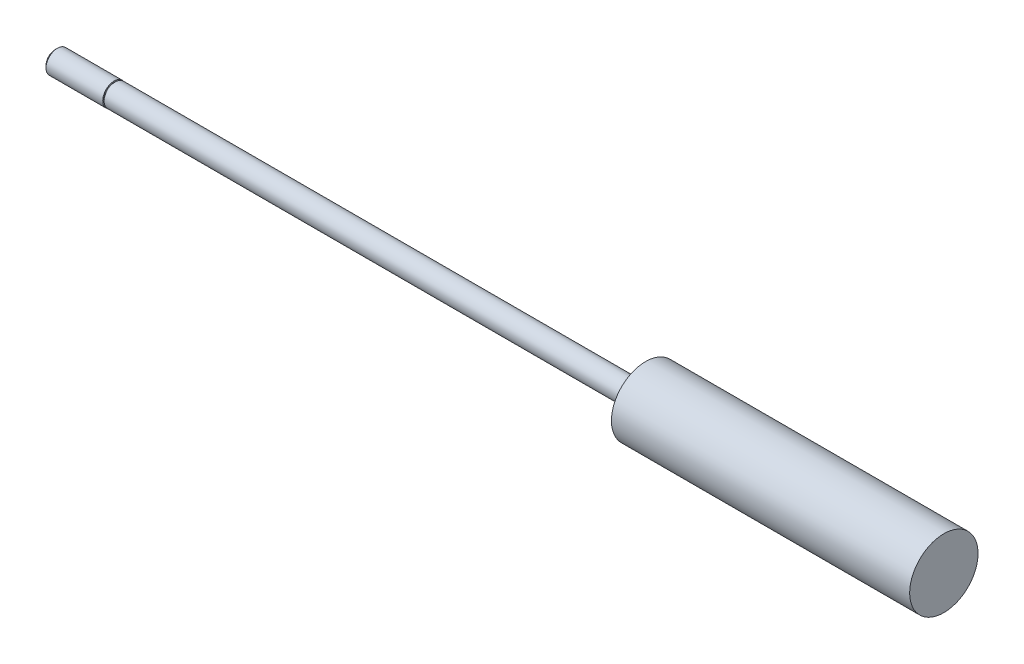
SolidWorks part; units mm, degrees
material "AISI 1045 Steel, cold drawn"
ref_plane "Front Plane" through (0, 0, 0) normal (0, 0, 1) x (1, 0, 0)
ref_plane "Top Plane" through (0, 0, 0) normal (0, 1, 0) x (1, 0, 0)
ref_plane "Right Plane" through (0, 0, 0) normal (1, 0, 0) x (0, 0, -1)
sketch "Sketch1" plane through (0, 0, 0) normal (0, 0, 1) x (1, 0, 0)
  line L0 (0, 0) -> (0, 2.3749)
  line L1 (0, 2.3749) -> (111.9124, 2.3749)
  line L2 (111.9124, 2.3749) -> (111.9124, 7.2199)
  line L3 (111.9124, 7.2199) -> (174.8536, 7.2199)
  line L4 (174.8536, 7.2199) -> (174.8536, 0)
  line L5 (174.8536, 0) -> (0, 0)
  line L6 (174.8536, 0) -> (0, 0) construction
revolve "Revolve1" add sketch "Sketch1" angle 360 about L6 reverse direction yes
sketch "Sketch2" plane through (0, 0, 0) normal (0, 0, 1) x (1, 0, 0)
  line L0 (-12.7, 0) -> (-12.7, 1.9406)
  line L1 (-12.7, 1.9406) -> (-12.2276, 2.413)
  line L2 (-12.2276, 2.413) -> (0, 2.413)
  line L3 (0, 2.413) -> (0, 0)
  line L4 (0, 0) -> (-12.7, 0)
  line L5 (0, 0) -> (-12.7, 0) construction
revolve "Revolve2" add sketch "Sketch2" angle 360 about L5 reverse direction yes
cosmetic thread "Cosmetic Thread1" parameters "D1"=12.7, "D2"=3.8811
ref_plane "Plane1" through (0, 0, 0) normal (1, 0, 0) x (0, 0, -1)
ref_plane "Plane2" through (0, 0, 0) normal (1, 0, 0) x (0, 0, -1)
ref_plane "Plane3" through (286.766, 0, 0) normal (1, 0, 0) x (0, 0, -1)
ref_plane "Plane4" through (-12.7, 0, 0) normal (1, 0, 0) x (0, 0, -1)
sketch "Sketch3" plane through (0, 0, 0) normal (0, 0, 1) x (1, 0, 0)
  line L0 (-0.254, 2.667) -> (-0.254, 2.159)
  line L1 (-0.254, 2.159) -> (0, 2.159)
  line L2 (0, 2.159) -> (0, 2.667)
  line L3 (0, 2.667) -> (-0.254, 2.667)
  line L4 (0, 0) -> (-0.254, 0) construction
revolve "Cut-Revolve1" cut sketch "Sketch3" angle 360 about L4 reverse direction yes
ref_plane "Plane5" through (0, 0, 0) normal (1, 0, 0) x (0, 0, -1)
ref_plane "Plane6" through (-12.7, 0, 0) normal (1, 0, 0) x (0, 0, -1)
ref_plane "dia1 XY" through (0, 0, 0) normal (1, 0, 0) x (0, 0, -1)
ref_plane "dia1 XZ" through (0, 2.3749, 0) normal (0, -1, 0) x (-1, 0, 0)
ref_plane "dia1 YZ" through (0, 0, 0) normal (0, 0, -1) x (-1, 0, 0)
ref_axis "dia1 X" through (0, 2.3749, 80.9) along (0, 0, -1)
ref_axis "dia1 Y" through (0, -50, 0) along (0, 1, 0)
ref_axis "dia1 Z" through (80.9, 2.3749, 0) along (-1, 0, 0)
sketch3d "dia1"
  point P0 (0, 2.3749, 0)
ref_plane "dia12 XY" through (0, 0, 0) normal (1, 0, 0) x (0, 0, -1)
ref_plane "dia12 XZ" through (0, 0, 0) normal (0, -1, 0) x (-1, 0, 0)
ref_plane "dia12 YZ" through (0, 0, 7.8105) normal (0, 0, -1) x (-1, 0, 0)
ref_axis "dia12 X" through (0, 0, 80.9) along (0, 0, -1)
ref_axis "dia12 Y" through (0, -50, 7.8105) along (0, 1, 0)
ref_axis "dia12 Z" through (80.9, 0, 7.8105) along (-1, 0, 0)
sketch3d "dia12"
  point P0 (0, 0, 7.8105)
ref_plane "dia2 XY" through (0, 0, 0) normal (1, 0, 0) x (0, 0, -1)
ref_plane "dia2 XZ" through (0, -2.3749, 0) normal (0, -1, 0) x (-1, 0, 0)
ref_plane "dia2 YZ" through (0, 0, 0) normal (0, 0, -1) x (-1, 0, 0)
ref_axis "dia2 X" through (0, -2.3749, 80.9) along (0, 0, -1)
ref_axis "dia2 Y" through (0, -50, 0) along (0, 1, 0)
ref_axis "dia2 Z" through (80.9, -2.3749, 0) along (-1, 0, 0)
sketch3d "dia2"
  point P0 (0, -2.3749, 0)
ref_plane "dia22 XY" through (0, 0, 0) normal (1, 0, 0) x (0, 0, -1)
ref_plane "dia22 XZ" through (0, 0, 0) normal (0, -1, 0) x (-1, 0, 0)
ref_plane "dia22 YZ" through (0, 0, -7.8105) normal (0, 0, -1) x (-1, 0, 0)
ref_axis "dia22 X" through (0, 0, 80.9) along (0, 0, -1)
ref_axis "dia22 Y" through (0, -50, -7.8105) along (0, 1, 0)
ref_axis "dia22 Z" through (80.9, 0, -7.8105) along (-1, 0, 0)
sketch3d "dia22"
  point P0 (0, 0, -7.8105)
ref_plane "rl1 XY" through (-12.7, 0, 0) normal (1, 0, 0) x (0, 0, -1)
ref_plane "rl1 XZ" through (0, 0, 0) normal (0, -1, 0) x (-1, 0, 0)
ref_plane "rl1 YZ" through (0, 0, 0) normal (0, 0, -1) x (-1, 0, 0)
ref_axis "rl1 X" through (-12.7, 0, 80.9) along (0, 0, -1)
ref_axis "rl1 Y" through (-12.7, -50, 0) along (0, 1, 0)
ref_axis "rl1 Z" through (80.9, 0, 0) along (-1, 0, 0)
sketch3d "rl1"
  point P0 (-12.7, 0, 0)
ref_plane "rl2 XY" through (0, 0, 0) normal (1, 0, 0) x (0, 0, -1)
ref_plane "rl2 XZ" through (0, 0, 0) normal (0, -1, 0) x (-1, 0, 0)
ref_plane "rl2 YZ" through (0, 0, 0) normal (0, 0, -1) x (-1, 0, 0)
ref_axis "rl2 X" through (0, 0, 80.9) along (0, 0, -1)
ref_axis "rl2 Y" through (0, -50, 0) along (0, 1, 0)
ref_axis "rl2 Z" through (80.9, 0, 0) along (-1, 0, 0)
sketch3d "rl2"
  point P0 (0, 0, 0)
ref_plane "rod_cp XY" through (0, 0, 0) normal (1, 0, 0) x (0, 0, -1)
ref_plane "rod_cp XZ" through (0, 0, 0) normal (0, -1, 0) x (-1, 0, 0)
ref_plane "rod_cp YZ" through (0, 0, 0) normal (0, 0, -1) x (-1, 0, 0)
ref_axis "rod_cp X" through (0, 0, 80.9) along (0, 0, -1)
ref_axis "rod_cp Y" through (0, -50, 0) along (0, 1, 0)
ref_axis "rod_cp Z" through (80.9, 0, 0) along (-1, 0, 0)
sketch3d "rod_cp"
  point P0 (0, 0, 0)
ref_plane "thd1 XY" through (-12.7, 0, 0) normal (1, 0, 0) x (0, 0, -1)
ref_plane "thd1 XZ" through (0, 2.413, 0) normal (0, -1, 0) x (-1, 0, 0)
ref_plane "thd1 YZ" through (0, 0, 0) normal (0, 0, -1) x (-1, 0, 0)
ref_axis "thd1 X" through (-12.7, 2.413, 80.9) along (0, 0, -1)
ref_axis "thd1 Y" through (-12.7, -50, 0) along (0, 1, 0)
ref_axis "thd1 Z" through (80.9, 2.413, 0) along (-1, 0, 0)
sketch3d "thd1"
  point P0 (-12.7, 2.413, 0)
ref_plane "thd2 XY" through (-12.7, 0, 0) normal (1, 0, 0) x (0, 0, -1)
ref_plane "thd2 XZ" through (0, -2.413, 0) normal (0, -1, 0) x (-1, 0, 0)
ref_plane "thd2 YZ" through (0, 0, 0) normal (0, 0, -1) x (-1, 0, 0)
ref_axis "thd2 X" through (-12.7, -2.413, 80.9) along (0, 0, -1)
ref_axis "thd2 Y" through (-12.7, -50, 0) along (0, 1, 0)
ref_axis "thd2 Z" through (80.9, -2.413, 0) along (-1, 0, 0)
sketch3d "thd2"
  point P0 (-12.7, -2.413, 0)
ref_plane "to_rod_clevis XY" through (-12.7, 0, 0) normal (1, 0, 0) x (0, 0, -1)
ref_plane "to_rod_clevis XZ" through (0, 0, 0) normal (0, -1, 0) x (-1, 0, 0)
ref_plane "to_rod_clevis YZ" through (0, 0, 0) normal (0, 0, -1) x (-1, 0, 0)
ref_axis "to_rod_clevis X" through (-12.7, 0, 80.9) along (0, 0, -1)
ref_axis "to_rod_clevis Y" through (-12.7, -50, 0) along (0, 1, 0)
ref_axis "to_rod_clevis Z" through (80.9, 0, 0) along (-1, 0, 0)
sketch3d "to_rod_clevis"
  point P0 (-12.7, 0, 0)
